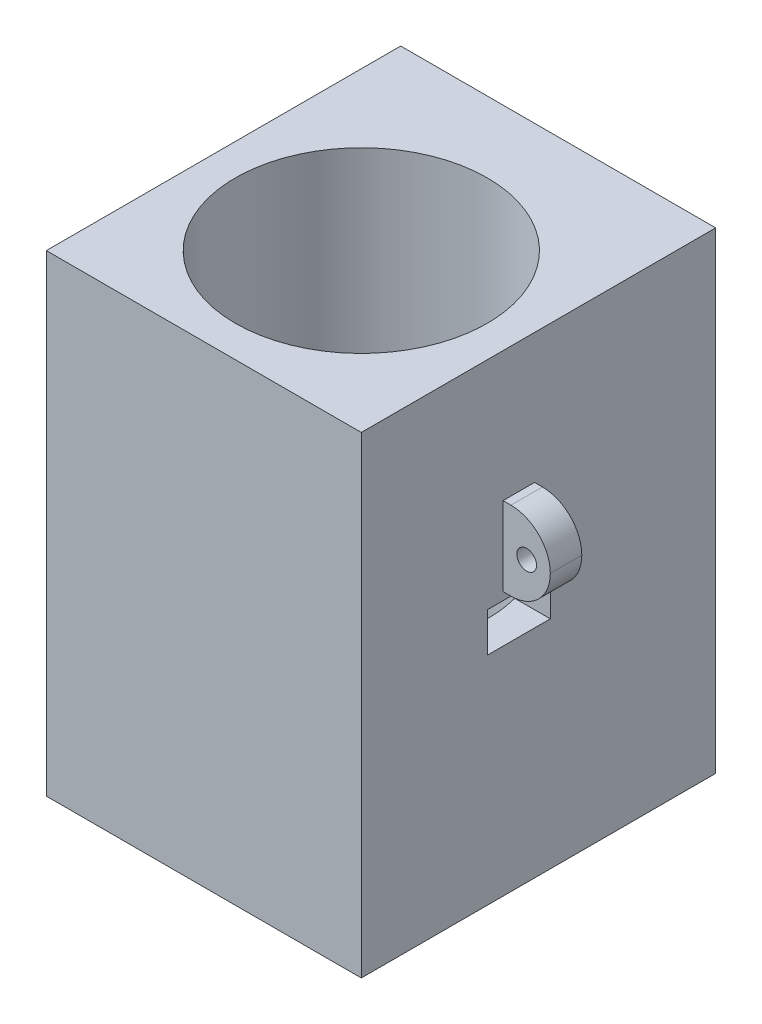
SolidWorks part; units mm, degrees
ref_plane "Alzado" through (0, 0, 0) normal (0, 0, 1) x (1, 0, 0)
ref_plane "Planta" through (0, 0, 0) normal (0, 1, 0) x (1, 0, 0)
ref_plane "Vista lateral" through (0, 0, 0) normal (1, 0, 0) x (0, 0, -1)
sketch "Croquis1" plane through (0, 0, 0) normal (0, 1, 0) x (1, 0, 0)
  line L0 (0, 27.427) -> (0, -25.1525) construction
  line L2 (-20, 25) -> (20, 25)
  line L3 (-20, 25) -> (-20, -20)
  line L4 (-20, -20) -> (20, -20)
  line L5 (20, 25) -> (20, -20)
  circle A0 centre (0, 0) radius 16
  circle A1 centre (0, 0) radius 20 construction
  dimension "D1" = 32
  dimension "D3" = 25
  dimension "D2" = 4
extrude "Saliente-Extruir1" add sketch "Croquis1" along normal mid plane 60
sketch "Croquis3" plane through (0, 0, 0) normal (1, 0, 0) x (0, 0, -1)
  line L1 (-4, -2.5) -> (4, -2.5)
  line L2 (-4, -2.5) -> (-4, 2.5)
  line L3 (-4, 2.5) -> (4, 2.5)
  line L4 (4, -2.5) -> (4, 2.5)
  line L5 (-4, -2.5) -> (4, 2.5) construction
  line L6 (-4, 2.5) -> (4, -2.5) construction
  point P0 (0, 0)
  dimension "D1" = 8
  dimension "D2" = 5
extrude "Cortar-Extruir1" cut sketch "Croquis3" against normal mid plane 80
sketch "Croquis4" plane through (0, 0, 0) normal (0, 0, 1) x (1, 0, 0)
  line L0 (0, 34.5317) -> (0, -36.4637) construction
  line L2 (-20, 30) -> (-20, -30) construction
  line L3 (26, 13.5) -> (20, 3.5) construction
  line L4 (-26, 3.5) -> (-20, 3.5)
  line L5 (-26, 3.5) -> (-26, 13.5)
  line L6 (-26, 13.5) -> (-20, 13.5)
  line L7 (-20, 3.5) -> (-20, 13.5)
  line L8 (-26, 3.5) -> (-20, 13.5) construction
  line L9 (-26, 13.5) -> (-20, 3.5) construction
  line L10 (26, 3.5) -> (20, 13.5) construction
  line L11 (20, 3.5) -> (20, 13.5)
  line L12 (26, 13.5) -> (20, 13.5)
  line L13 (26, 3.5) -> (26, 13.5)
  line L14 (26, 3.5) -> (20, 3.5)
  line L15 (27.1984, 0) -> (-38.9004, 0) construction
  circle A0 centre (-23, 8.5) radius 1.25
  circle A1 centre (23, 8.5) radius 1.25
  dimension "D3" = 2.5
  dimension "D1" = 8.5
  dimension "D2" = 3
  dimension "D4" = 5
extrude "Saliente-Extruir2" add sketch "Croquis4" along normal mid plane 4
fillet "Redondeo1" radius 5 4 edges at (26, 3.5, 0) (26, 13.5, 0) (-26, 3.5, 0) (-26, 13.5, 0)
